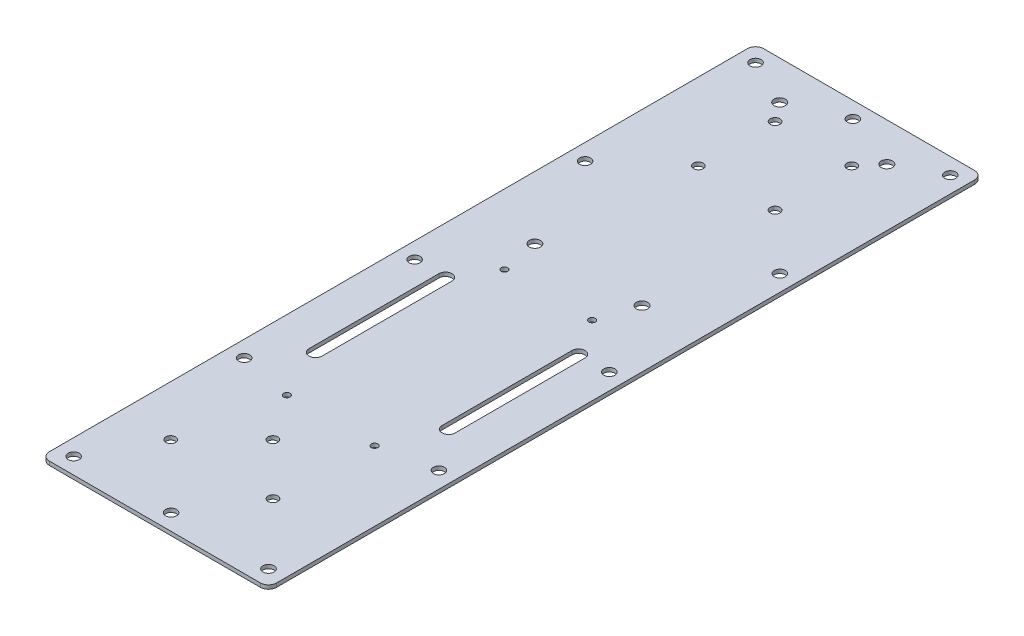
SolidWorks part; units mm, degrees
ref_plane "Front Plane" through (0, 0, 0) normal (0, 0, 1) x (1, 0, 0)
ref_plane "Top Plane" through (0, 0, 0) normal (0, 1, 0) x (1, 0, 0)
ref_plane "Right Plane" through (0, 0, 0) normal (1, 0, 0) x (0, 0, -1)
sketch "Sketch2" plane through (0, 0, 0) normal (0, 1, 0) x (1, 0, 0)
  line L0 (-44.45, 0) -> (44.45, 0) construction
  line L1 (-41.275, 139.7) -> (41.275, 139.7)
  line L2 (-44.45, 136.525) -> (-44.45, -136.525)
  line L3 (-41.275, -139.7) -> (41.275, -139.7)
  line L4 (44.45, 136.525) -> (44.45, -136.525)
  line L5 (0, 139.7) -> (0, -139.7) construction
  arc A0 (-44.45, -136.525) -> (-41.275, -139.7) centre (-41.275, -136.525) ccw
  arc A1 (41.275, -139.7) -> (44.45, -136.525) centre (41.275, -136.525) ccw
  arc A2 (41.275, 139.7) -> (44.45, 136.525) centre (41.275, 136.525) cw
  arc A3 (-41.275, 139.7) -> (-44.45, 136.525) centre (-41.275, 136.525) ccw
  point P8 (0, 0)
  point P13 (-44.45, -139.7)
  point P16 (44.45, -139.7)
  point P21 (-44.45, 139.7)
  dimension "D3" = 3.175
  dimension "D1" = 279.4
  dimension "D2" = 88.9
extrude "Plate Thickness" add sketch "Sketch2" along normal blind 1.5 contours L2 A0 L3 A1 L4 A2 L1 A3
sketch "Sketch3" plane through (0, 1.5, 0) normal (0, 1, 0) x (1, 0, 0)
  line L0 (-44.45, 136.525) -> (-44.45, -136.525) construction
  line L1 (-41.275, 139.7) -> (41.275, 139.7) construction
  line L4 (0, 139.7) -> (0, -139.7) construction
  line L5 (-41.275, -139.7) -> (41.275, -139.7) construction
  circle A0 centre (-38.1, 133.35) radius 2.159
  circle A1 centre (-38.1, 66.675) radius 2.159
  circle A2 centre (-38.1, -66.675) radius 2.159
  circle A3 centre (-38.1, -133.35) radius 2.159
  circle A4 centre (38.1, -133.35) radius 2.159
  circle A5 centre (38.1, -66.675) radius 2.159
  circle A6 centre (38.1, 66.675) radius 2.159
  circle A7 centre (38.1, 133.35) radius 2.159
  circle A8 centre (0, 133.35) radius 2.159
  circle A9 centre (0, -133.35) radius 2.159
  circle A10 centre (-38.1, 0) radius 2.159
  circle A11 centre (38.1, 0) radius 2.159
  point P6 (0, 0)
  point P9 (-38.1, 0)
  point P18 (0, 0)
  point P33 (0, 0)
  dimension "D1" = 4.318
  dimension "D4" = 4.318
  dimension "D2" = 6.35
  dimension "D3" = 6.35
  dimension "D5" = 66.675
  dimension "D6" = 6.35
  dimension "D7" = 66.675
extrude "Mounting holes" cut sketch "Sketch3" against normal through all
sketch "Sketch4" plane through (0, 1.5, 0) normal (0, 1, 0) x (1, 0, 0)
  line L0 (-19.9374, 28.8942) -> (21.9726, 28.8942) construction
  line L1 (1.0176, 0) -> (1.0176, 139.7) construction
  circle A0 centre (-19.9374, 124.6522) radius 2.2225
  circle A1 centre (-19.9374, 28.8942) radius 2.2225
  circle A2 centre (21.9726, 28.8942) radius 2.2225
  circle A3 centre (21.9726, 124.6522) radius 2.2225
  point P13 (1.0176, 28.8942)
  dimension "D1" = 4.445
  dimension "D2" = 95.758
  dimension "D3" = 41.91
extrude "Jetson Holes (w/ mount)" cut sketch "Sketch4" against normal through all
sketch "Sketch5" plane through (0, 1.5, 0) normal (0, 1, 0) x (1, 0, 0)
  circle A1 centre (-14.3419, 117.2351) radius 1.905
  circle A3 centre (15.6555, 117.2351) radius 1.905
  circle A4 centre (15.6555, 87.2377) radius 1.905
  circle A5 centre (-14.3419, 87.2377) radius 1.905
  point P2 (-13.8137, 113.1249)
  point P9 (15.6555, 117.2351)
  dimension "D1" = 3.81
  dimension "D2" = 29.9974
  dimension "D3" = 29.9974
extrude "PDB holes" cut sketch "Sketch5" against normal through all
sketch "Sketch6" plane through (0, 1.5, 0) normal (0, 1, 0) x (1, 0, 0)
  circle A3 centre (-24.7939, -108.7175) radius 1.905
  circle A4 centre (15.2111, -108.7175) radius 1.905
  circle A5 centre (-4.8041, -88.7277) radius 1.905
  point P6 (-24.7939, -108.7175)
  dimension "D1" = 3.81
  dimension "D2" = 40.005
  dimension "D3" = 19.9898
  dimension "D4" = 19.9898
extrude "Lidar Holes" cut sketch "Sketch6" against normal through all
sketch "Sketch7" plane through (0, 1.5, 0) normal (0, 1, 0) x (1, 0, 0)
  line L0 (0, 139.7) -> (0, -139.7) construction
  line L1 (-41.275, 139.7) -> (41.275, 139.7) construction
  line L2 (-41.275, -139.7) -> (41.275, -139.7) construction
  line L3 (17.145, 14.1724) -> (-17.145, 14.1724) construction
  circle A0 centre (-17.145, 14.1724) radius 1.27
  circle A1 centre (-17.145, -70.9176) radius 1.27
  circle A2 centre (17.145, -70.9176) radius 1.27
  circle A3 centre (17.145, 14.1724) radius 1.27
  point P14 (0, 14.1724)
  dimension "D1" = 2.54
  dimension "D2" = 85.09
  dimension "D3" = 34.29
extrude "PixHawk Holes" cut sketch "Sketch7" against normal through all
sketch "Sketch8" plane through (0, 1.5, 0) normal (0, 1, 0) x (1, 0, 0)
  line L0 (0, 139.7) -> (0, -115.5095) construction
  line L1 (-41.275, 139.7) -> (41.275, 139.7) construction
  line L2 (-26.035, -0.006) -> (-26.035, -50.806) construction
  line L3 (-23.495, -0.006) -> (-23.495, -50.806)
  line L4 (-28.575, -0.006) -> (-28.575, -50.806)
  line L5 (26.035, -0.006) -> (26.035, -50.806) construction
  line L6 (23.495, -0.006) -> (23.495, -50.806)
  line L7 (28.575, -0.006) -> (28.575, -50.806)
  arc A0 (-23.495, -0.006) -> (-28.575, -0.006) centre (-26.035, -0.006) ccw
  arc A1 (-28.575, -50.806) -> (-23.495, -50.806) centre (-26.035, -50.806) ccw
  arc A2 (23.495, -0.006) -> (28.575, -0.006) centre (26.035, -0.006) cw
  arc A3 (28.575, -50.806) -> (23.495, -50.806) centre (26.035, -50.806) cw
  point P7 (-26.035, -25.406)
  point P14 (26.035, -25.406)
  dimension "D1" = 50.8
  dimension "D2" = 5.08
  dimension "D3" = 26.035
extrude "Battery Holes" cut sketch "Sketch8" against normal through all
